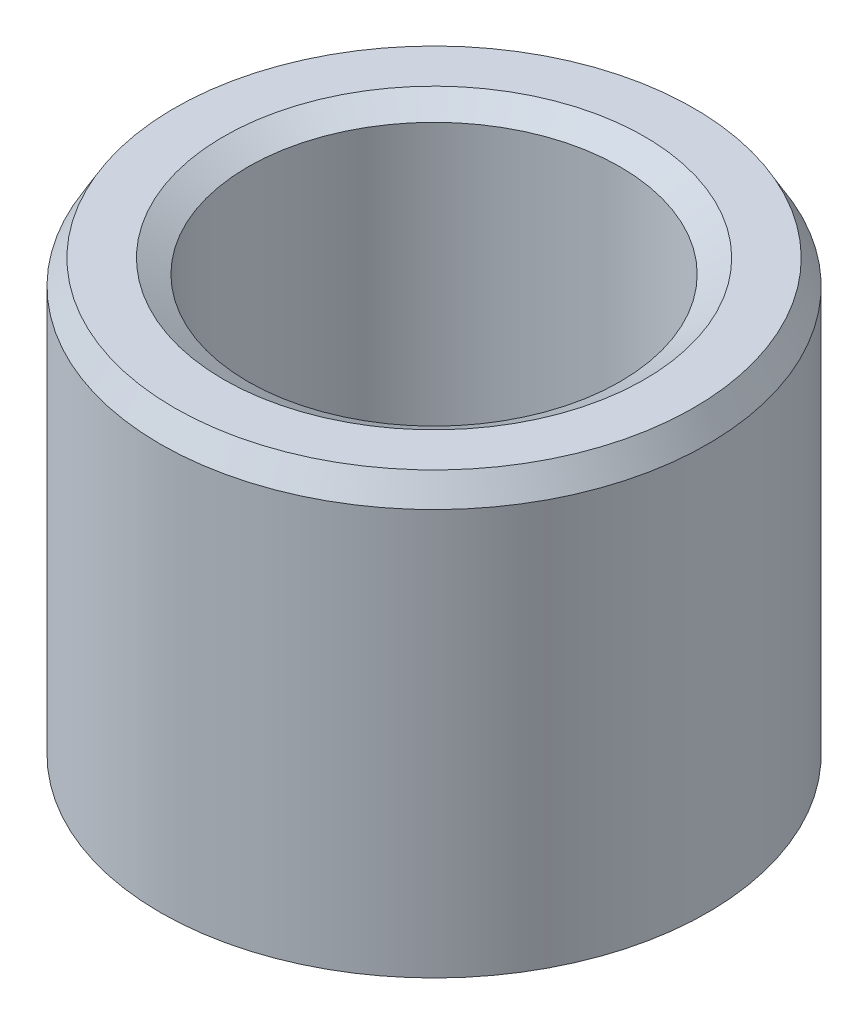
SolidWorks part; units mm, degrees
ref_plane "Front Plane" through (0, 0, 0) normal (0, 0, 1) x (1, 0, 0)
ref_plane "Top Plane" through (0, 0, 0) normal (0, 1, 0) x (1, 0, 0)
ref_plane "Right Plane" through (0, 0, 0) normal (1, 0, 0) x (0, 0, -1)
sketch "Sketch1" plane through (0, 0, 0) normal (0, 1, 0) x (1, 0, 0)
  circle A0 centre (0, 0) radius 10
  dimension "SLEEVE_OD" = 20
extrude "Boss-Extrude1" add sketch "Sketch1" along normal blind 16.2249
sketch "Sketch2" plane through (0, 0, 0) normal (0, 1, 0) x (1, 0, 0)
  circle A0 centre (0, 0) radius 6.7985
  dimension "BORE_D" = 13.5969
extrude "Cut-Extrude1" cut sketch "Sketch2" along normal through all
chamfer "Chamfer1" distance 0.8907 angle 30 4 edges at (0, 16.2249, 6.7985) (0, 0, 6.7985) (0, 0, 10) (0, 16.2249, 10) first distance on face at (0, 16.2249, 6.7985) first distance on face at (0, 0, 6.7985) first distance on face at (0, 16.2249, 10)
